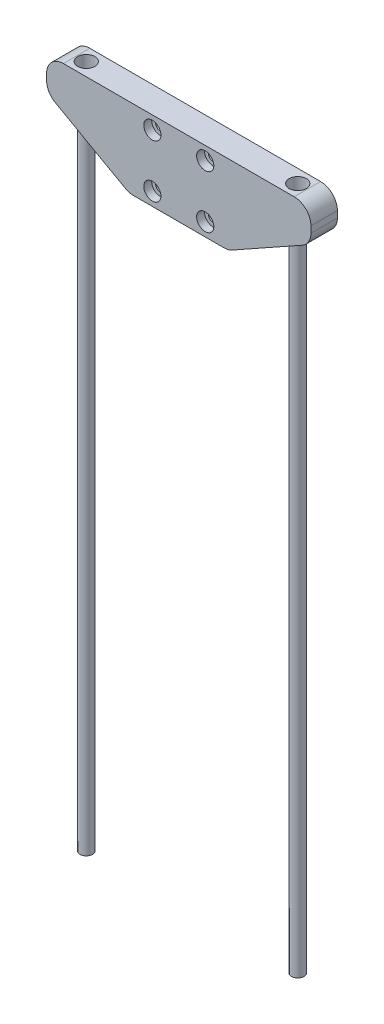
SolidWorks part; units mm, degrees
other "Markup2"
sketch "Sketch8"
other "Markup3"
sketch "Sketch15"
ref_plane "Front Plane" through (0, 0, 0) normal (0, 0, 1) x (1, 0, 0)
ref_plane "Top Plane" through (0, 0, 0) normal (0, 1, 0) x (1, 0, 0)
ref_plane "Right Plane" through (0, 0, 0) normal (1, 0, 0) x (0, 0, -1)
sketch "Sketch2" plane through (0, 0, 0) normal (0, 0, 1) x (1, 0, 0)
  line L0 (-40, 0) -> (-40, -243.6) construction
  line L1 (40, 0) -> (40, -243.6) construction
  line L2 (0, 48.6067) -> (0, -93.2297) construction
  line L3 (-50, 15) -> (-50, 2.5)
  line L4 (-50, 2.5) -> (-18.75, -15)
  line L5 (-18.75, -15) -> (18.75, -15)
  line L6 (18.75, -15) -> (50, 2.5)
  line L7 (-50, 15) -> (50, 15)
  line L8 (50, 15) -> (50, 2.5)
  line L10 (-42.3812, 0) -> (-37.6188, 0)
  line L11 (-42.3812, 0) -> (-42.3812, -243.6)
  line L12 (-42.3812, -243.6) -> (-37.6187, -243.6)
  line L13 (-37.6188, 0) -> (-37.6187, -243.6)
  line L14 (-10, 10) -> (10, 10) construction
  line L15 (-10, 10) -> (-10, -10) construction
  line L16 (-10, -10) -> (10, -10) construction
  line L17 (10, 10) -> (10, -10) construction
  line L18 (37.6188, -243.6) -> (42.3813, -243.6)
  line L19 (37.6188, -243.6) -> (37.6188, 0)
  line L20 (37.6188, 0) -> (42.3812, 0)
  line L21 (42.3813, -243.6) -> (42.3812, 0)
  dimension "D1" = 80
  dimension "D3" = 4.7625
  dimension "D4" = 20
  dimension "D5" = 20
  dimension "D6" = 228.6
  dimension "D7" = 15
  dimension "D8" = 15
  dimension "D9" = 5
  dimension "D10" = 12.5
  dimension "D11" = 100
  dimension "D12" = 37.5
sketch "Sketch9" plane through (0, 0, 0) normal (0, 1, 0) x (1, 0, 0)
  line L0 (-40, 0) -> (-35, 0) construction
  line L2 (-40, 2.3812) -> (-35, 2.3812)
  line L3 (-40, -2.3812) -> (-35, -2.3812)
  line L4 (0, 20.7896) -> (0, -26.7229) construction
  line L5 (40, 0) -> (35, 0) construction
  line L6 (40, 2.3813) -> (35, 2.3813)
  line L7 (40, -2.3813) -> (35, -2.3813)
  line L8 (-37.5, 2.3812) -> (-37.5, -2.3812) construction
  line L9 (-42.3812, 0) -> (-37.6187, 0) construction
  line L10 (37.5, 2.3813) -> (37.5, -2.3813) construction
  arc A0 (-40, 2.3812) -> (-40, -2.3812) centre (-40, 0) ccw
  arc A1 (-35, -2.3812) -> (-35, 2.3812) centre (-35, 0) ccw
  arc A2 (40, 2.3813) -> (40, -2.3813) centre (40, 0) cw
  arc A3 (35, -2.3813) -> (35, 2.3813) centre (35, 0) cw
  circle A4 centre (-40, 0) radius 1.5
  circle A5 centre (40, 0) radius 1.5
  point P5 (-37.5, 0)
  point P15 (37.5, 0)
  dimension "D1" = 5
  dimension "D3" = 3
  dimension "D2" = 4.7625
sketch "Sketch3" plane through (0, 0, 0) normal (0, 0, 1) x (1, 0, 0)
  line L0 (-50, 15) -> (-50, 2.5) construction
  line L1 (-50, 2.5) -> (-18.75, -15) construction
  line L2 (-18.75, -15) -> (18.75, -15) construction
  line L3 (18.75, -15) -> (50, 2.5) construction
  line L4 (50, 15) -> (50, 2.5) construction
  line L5 (-50, 15) -> (50, 15) construction
  line L6 (-50, 15) -> (-50, 2.5)
  line L7 (-50, 2.5) -> (-18.75, -15)
  line L8 (-18.75, -15) -> (18.75, -15)
  line L9 (18.75, -15) -> (50, 2.5)
  line L10 (50, 15) -> (50, 2.5)
  line L11 (-50, 15) -> (50, 15)
extrude "Boss-Extrude1" add sketch "Sketch3" along normal mid plane 10
sketch "Sketch10" plane through (0, 0, 0) normal (0, 1, 0) x (1, 0, 0)
  line L0 (40, 2.3813) -> (35, 2.3813) construction
  line L1 (40, -2.3813) -> (35, -2.3813) construction
  line L2 (-40, 2.3812) -> (-35, 2.3812) construction
  line L3 (-40, -2.3812) -> (-35, -2.3812) construction
  line L4 (40, 2.3813) -> (35, 2.3813)
  line L5 (40, -2.3813) -> (35, -2.3813)
  line L6 (-40, 2.3812) -> (-35, 2.3812)
  line L7 (-40, -2.3812) -> (-35, -2.3812)
  arc A0 (35, 2.3813) -> (35, -2.3813) centre (35, 0) ccw construction
  arc A1 (40, -2.3813) -> (40, 2.3813) centre (40, 0) ccw construction
  arc A2 (-35, -2.3812) -> (-35, 2.3812) centre (-35, 0) ccw construction
  arc A3 (-40, 2.3812) -> (-40, -2.3812) centre (-40, 0) ccw construction
  arc A4 (35, 2.3813) -> (35, -2.3813) centre (35, 0) ccw
  arc A5 (40, -2.3813) -> (40, 2.3813) centre (40, 0) ccw
  arc A6 (-35, -2.3812) -> (-35, 2.3812) centre (-35, 0) ccw
  arc A7 (-40, 2.3812) -> (-40, -2.3812) centre (-40, 0) ccw
extrude "Cut-Extrude1" cut sketch "Sketch10" against normal blind 10
sketch "Sketch4" plane through (0, 0, 0) normal (0, 0, 1) x (1, 0, 0)
  line L0 (40, 0) -> (40, -243.6) construction
  line L1 (-40, 0) -> (-40, -243.6) construction
  line L2 (-42.3812, 0) -> (-42.3812, -243.6) construction
  line L3 (-42.3812, -243.6) -> (-37.6187, -243.6) construction
  line L4 (-37.6188, 0) -> (-37.6187, -243.6) construction
  line L5 (-42.3812, 0) -> (-37.6188, 0) construction
  line L6 (40, 0) -> (40, -243.6)
  line L7 (-40, 0) -> (-40, -243.6)
  line L8 (-42.3812, 0) -> (-42.3812, -243.6)
  line L9 (-42.3812, -243.6) -> (-40, -243.6)
  line L10 (-37.6188, 0) -> (-37.6187, -243.6) construction
  line L11 (-42.3812, 0) -> (-40, 0)
  line L12 (-40, -243.6) -> (-40, -275.6996) construction
  line L13 (-40, -243.6) -> (-37.6187, -243.6) construction
  line L14 (-40, 0) -> (-37.6188, 0) construction
  line L15 (40, -243.6) -> (40, -281.3243) construction
  line L16 (37.6188, -243.6) -> (42.3813, -243.6)
  line L17 (37.6188, -243.6) -> (37.6188, 0)
  line L18 (37.6188, 0) -> (42.3812, 0)
  line L19 (42.3813, -243.6) -> (42.3812, 0)
  line L20 (37.6188, -247.4505) -> (40, -247.4505) construction
revolve "Revolve1" add sketch "Sketch4" angle 360 about L12 region at (-41.1906, -121.8, 0)
revolve "Revolve2" add sketch "Sketch4<3>" angle 360 about L15 region at (38.8094, -121.8, 0)
sketch "Sketch4<3>" plane through (0, 0, 0) normal (0, 0, 1) x (1, 0, 0) same geometry as "Sketch4"
hole_wizard "CBORE for M3 SHCS1" positions "Sketch5" profile "Sketch6" counterbore size "M3" standard "ANSI Metric"
sketch "Sketch5" plane through (0, 0, 5) normal (0, 0, 1) x (1, 0, 0)
  point P0 (-10, 10)
  point P3 (-10, -10)
  point P6 (10, -10)
  point P9 (10, 10)
sketch "Sketch6" plane through (-10, 10, 5) normal (1, 0, 0) x (0, -1, 0)
  line L0 (0, 0) -> (0, 8.5815)
  line L1 (0, 8.5815) -> (1.8, 7.5)
  line L2 (1.8, 7.5) -> (1.8, 3)
  line L3 (1.8, 3) -> (3.25, 3)
  line L4 (3.25, 3) -> (3.25, 0)
  line L5 (3.25, 0) -> (0, 0)
  line L10 (0, 8.5815) -> (-1.8, 7.5) construction
  line L11 (0, -6.35) -> (0, 107.95) construction
  dimension "Hole Dia." = 3.6
  dimension "Hole Depth" = 7.5
  dimension "C'Bore Dia." = 6.5
  dimension "C'Bore Depth" = 3
  dimension "Drill Angle" = 118
hole_wizard "CBORE for M3 SHCS2" positions "Sketch11" profile "Sketch12" counterbore size "M3" standard "ANSI Metric" end condition through all
sketch "Sketch11" plane through (0, 15, 0) normal (0, 1, 0) x (1, 0, 0)
  point P0 (-40, 0)
  point P3 (40, 0)
sketch "Sketch12" plane through (-40, 15, 0) normal (1, 0, 0) x (0, 0, 1)
  line L0 (0, 0) -> (0, 258.6)
  line L1 (0, 258.6) -> (1.8, 258.6)
  line L3 (1.8, 258.6) -> (1.8, 11)
  line L4 (1.8, 11) -> (3.25, 11)
  line L5 (3.25, 11) -> (3.25, 0)
  line L7 (3.25, 0) -> (0, 0)
  line L11 (0, -6.35) -> (0, 107.95) construction
  dimension "Thru Hole Dia." = 3.6
  dimension "Thru Hole Depth" = 258.6
  dimension "C'Bore Dia." = 6.5
  dimension "C'Bore Depth" = 11
hole_wizard "M3x0.5 Tapped Hole1" positions "Sketch13" profile "Sketch14" tap size "M3x0.5" standard "ANSI Metric"
sketch "Sketch13" plane through (0, 0, 0) normal (0, 1, 0) x (1, 0, 0)
  point P0 (-40, 0)
  point P3 (40, 0)
sketch "Sketch14" plane through (-40, 0, 0) normal (1, 0, 0) x (0, 0, 1)
  line L0 (0, 0) -> (0, 8.2511)
  line L1 (0, 8.2511) -> (1.25, 7.5)
  line L2 (1.25, 7.5) -> (1.25, 0)
  line L5 (1.25, 0) -> (0, 0)
  line L10 (0, 8.2511) -> (-1.25, 7.5) construction
  line L11 (0, -6.35) -> (0, 107.95) construction
  dimension "Tap Drill Dia." = 2.5
  dimension "Tap Drill Depth" = 7.5
  dimension "Drill Angle" = 118
fillet "Fillet1" radius 6.35 6 edges at (-18.75, -15, 0) (18.75, -15, 0) (50, 2.5, 0) (50, 15, 0) (-50, 15, 0) (-50, 2.5, 0)
